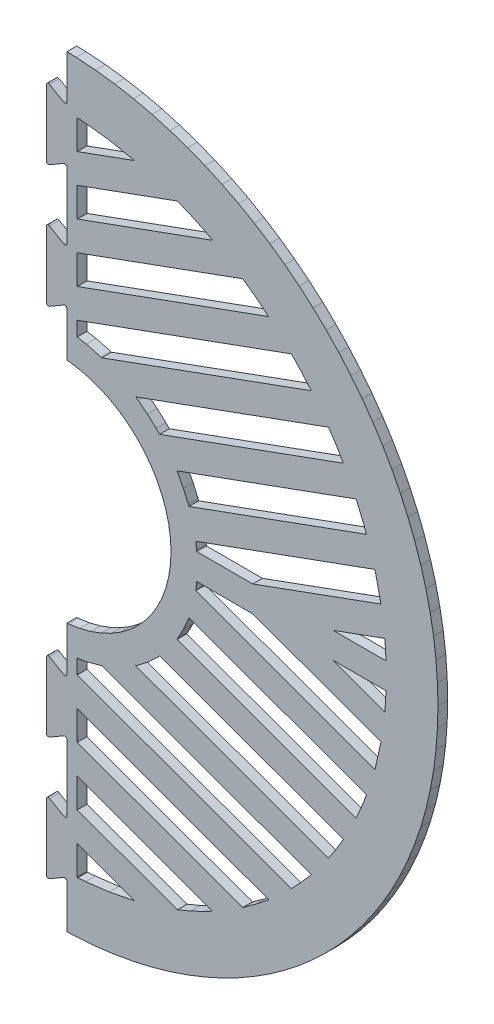
SolidWorks part; units mm, degrees
ref_plane "Front Plane" through (0, 0, 0) normal (0, 0, 1) x (1, 0, 0)
ref_plane "Top Plane" through (0, 0, 0) normal (0, 1, 0) x (1, 0, 0)
ref_plane "Right Plane" through (0, 0, 0) normal (1, 0, 0) x (0, 0, -1)
sketch "Model" plane through (0, 0, 0) normal (0, 0, 1) x (1, 0, 0)
  line L0 (-29.1025, -97.3667) -> (-27.1353, -97.9361)
  line L1 (-27.1353, -97.9361) -> (-21.8097, -99.2536)
  line L2 (-21.8097, -99.2536) -> (-16.3779, -100.2869)
  line L3 (-16.3779, -100.2869) -> (-10.848, -101.0278)
  line L4 (-10.848, -101.0278) -> (-5.2283, -101.4679)
  line L5 (-5.2283, -101.4679) -> (-4, -101.5146)
  line L6 (-4, -101.5146) -> (-4, -97.3667)
  line L7 (-4, -97.3667) -> (-29.1025, -97.3667)
  line L8 (4, -91.5563) -> (4, -100.5663)
  line L9 (4, -100.5663) -> (6.4923, -101.4734)
  line L10 (6.4923, -101.4734) -> (8.9399, -101.2903)
  line L11 (8.9399, -101.2903) -> (16.2223, -100.3929)
  line L12 (16.2223, -100.3929) -> (23.3353, -98.9929)
  line L13 (23.3353, -98.9929) -> (23.9888, -98.8316)
  line L14 (23.9888, -98.8316) -> (4, -91.5563)
  line L15 (-62.0452, -80.4333) -> (-59.3119, -82.4998)
  line L16 (-59.3119, -82.4998) -> (-55.4039, -85.1786)
  line L17 (-55.4039, -85.1786) -> (-51.3677, -87.677)
  line L18 (-51.3677, -87.677) -> (-49.1681, -88.9)
  line L19 (-49.1681, -88.9) -> (-4, -88.9)
  line L20 (-4, -88.9) -> (-4, -80.4333)
  line L21 (-4, -80.4333) -> (-62.0452, -80.4333)
  line L22 (4, -73.5362) -> (4, -82.5462)
  line L23 (4, -82.5462) -> (37.2469, -94.6471)
  line L24 (37.2469, -94.6471) -> (41.3341, -92.9428)
  line L25 (41.3341, -92.9428) -> (45.5839, -90.9334)
  line L26 (45.5839, -90.9334) -> (48.1117, -89.5915)
  line L27 (48.1117, -89.5915) -> (4, -73.5362)
  line L28 (-79.2988, -63.5) -> (-76.7248, -66.6048)
  line L29 (-76.7248, -66.6048) -> (-73.5451, -70.098)
  line L30 (-73.5451, -70.098) -> (-71.6792, -71.9667)
  line L31 (-71.6792, -71.9667) -> (-4, -71.9667)
  line L32 (-4, -71.9667) -> (-4, -63.5)
  line L33 (-4, -63.5) -> (-79.2988, -63.5)
  line L34 (4, -55.5161) -> (4, -64.5262)
  line L35 (4, -64.5262) -> (57.3994, -83.962)
  line L36 (57.3994, -83.962) -> (57.6454, -83.8007)
  line L37 (57.6454, -83.8007) -> (61.4183, -81.0733)
  line L38 (61.4183, -81.0733) -> (65.0584, -78.18)
  line L39 (65.0584, -78.18) -> (65.4148, -77.8693)
  line L40 (65.4148, -77.8693) -> (4, -55.5161)
  line L41 (-90.3108, -46.5667) -> (-90.0607, -47.0729)
  line L42 (-90.0607, -47.0729) -> (-87.7545, -51.2354)
  line L43 (-87.7545, -51.2354) -> (-85.4115, -55.0333)
  line L44 (-85.4115, -55.0333) -> (-4, -55.0333)
  line L45 (-4, -55.0333) -> (-4, -46.5667)
  line L46 (-4, -46.5667) -> (-90.3108, -46.5667)
  line L47 (13.9184, -41.106) -> (13.6646, -41.1963)
  line L48 (13.6646, -41.1963) -> (9.1415, -42.427)
  line L49 (9.1415, -42.427) -> (4.4365, -43.1676)
  line L50 (4.4365, -43.1676) -> (4, -43.2008)
  line L51 (4, -43.2008) -> (4, -46.5061)
  line L52 (4, -46.5061) -> (72.4083, -71.4047)
  line L53 (72.4083, -71.4047) -> (75.1264, -68.5601)
  line L54 (75.1264, -68.5601) -> (78.18, -65.0584)
  line L55 (78.18, -65.0584) -> (78.5271, -64.6217)
  line L56 (78.5271, -64.6217) -> (13.9184, -41.106)
  line L57 (-97.2071, -29.6333) -> (-96.5817, -31.625)
  line L58 (-96.5817, -31.625) -> (-95.8036, -33.9098)
  line L59 (-95.8036, -33.9098) -> (-94.207, -38.1)
  line L60 (-94.207, -38.1) -> (-20.7604, -38.1)
  line L61 (-20.7604, -38.1) -> (-21.4848, -37.7079)
  line L62 (-21.4848, -37.7079) -> (-23.9895, -36.1628)
  line L63 (-23.9895, -36.1628) -> (-26.3777, -34.4565)
  line L64 (-26.3777, -34.4565) -> (-28.6418, -32.5965)
  line L65 (-28.6418, -32.5965) -> (-30.7744, -30.5904)
  line L66 (-30.7744, -30.5904) -> (-31.6842, -29.6333)
  line L67 (-31.6842, -29.6333) -> (-97.2071, -29.6333)
  line L68 (31.7453, -29.5744) -> (30.6825, -30.6825)
  line L69 (30.6825, -30.6825) -> (28.0009, -33.1492)
  line L70 (28.0009, -33.1492) -> (25.1189, -35.3861)
  line L71 (25.1189, -35.3861) -> (24.3655, -35.8984)
  line L72 (24.3655, -35.8984) -> (83.8612, -57.5531)
  line L73 (83.8612, -57.5531) -> (86.3569, -53.745)
  line L74 (86.3569, -53.745) -> (88.4468, -50.2121)
  line L75 (88.4468, -50.2121) -> (31.7453, -29.5744)
  line L76 (40.7776, -14.8418) -> (40.5732, -15.4165)
  line L77 (40.5732, -15.4165) -> (39.1128, -18.8121)
  line L78 (39.1128, -18.8121) -> (37.3789, -22.0511)
  line L79 (37.3789, -22.0511) -> (37.0937, -22.511)
  line L80 (37.0937, -22.511) -> (92.3359, -42.6176)
  line L81 (92.3359, -42.6176) -> (92.9428, -41.3341)
  line L82 (92.9428, -41.3341) -> (94.7589, -36.9789)
  line L83 (94.7589, -36.9789) -> (95.5572, -34.78)
  line L84 (95.5572, -34.78) -> (40.7776, -14.8418)
  line L85 (-100.8122, -12.7) -> (-100.5006, -14.9994)
  line L86 (-100.5006, -14.9994) -> (-99.6609, -19.8552)
  line L87 (-99.6609, -19.8552) -> (-99.3846, -21.1667)
  line L88 (-99.3846, -21.1667) -> (-37.8853, -21.1667)
  line L89 (-37.8853, -21.1667) -> (-38.7638, -19.5198)
  line L90 (-38.7638, -19.5198) -> (-40.0074, -16.8291)
  line L91 (-40.0074, -16.8291) -> (-41.069, -14.0429)
  line L92 (-41.069, -14.0429) -> (-41.4935, -12.7)
  line L93 (-41.4935, -12.7) -> (-100.8122, -12.7)
  line L94 (85.2546, -4) -> (101.2046, -9.8053)
  line L95 (101.2046, -9.8053) -> (101.2903, -8.9399)
  line L96 (101.2903, -8.9399) -> (101.6001, -4)
  line L97 (101.6001, -4) -> (85.2546, -4)
  line L98 (43.2008, -4) -> (43.1676, -4.4365)
  line L99 (43.1676, -4.4365) -> (42.932, -6.3385)
  line L100 (42.932, -6.3385) -> (42.8879, -6.5999)
  line L101 (42.8879, -6.5999) -> (98.134, -26.7078)
  line L102 (98.134, -26.7078) -> (98.4177, -25.6655)
  line L103 (98.4177, -25.6655) -> (99.9812, -18.6131)
  line L104 (99.9812, -18.6131) -> (100.0206, -18.3844)
  line L105 (100.0206, -18.3844) -> (60.4997, -4)
  line L106 (60.4997, -4) -> (43.2008, -4)
  line L107 (-101.5066, 4.2333) -> (-101.5689, 2.5406)
  line L108 (-101.5689, 2.5406) -> (-101.6001, 0)
  line L109 (-101.6001, 0) -> (-101.5689, -2.5406)
  line L110 (-101.5689, -2.5406) -> (-101.5066, -4.2333)
  line L111 (-101.5066, -4.2333) -> (-43.1862, -4.2333)
  line L112 (-43.1862, -4.2333) -> (-43.1946, -4.1628)
  line L113 (-43.1946, -4.1628) -> (-43.342, -2.0942)
  line L114 (-43.342, -2.0942) -> (-43.3917, 0)
  line L115 (-43.3917, 0) -> (-43.342, 2.0942)
  line L116 (-43.342, 2.0942) -> (-43.1946, 4.1628)
  line L117 (-43.1946, 4.1628) -> (-43.1862, 4.2333)
  line L118 (-43.1862, 4.2333) -> (-101.5066, 4.2333)
  line L119 (101.2046, 9.8053) -> (85.2546, 4)
  line L120 (85.2546, 4) -> (101.6001, 4)
  line L121 (101.6001, 4) -> (101.2903, 8.9399)
  line L122 (101.2903, 8.9399) -> (101.2046, 9.8053)
  line L123 (-99.3846, 21.1667) -> (-99.6609, 19.8552)
  line L124 (-99.6609, 19.8552) -> (-100.5006, 14.9994)
  line L125 (-100.5006, 14.9994) -> (-100.8122, 12.7)
  line L126 (-100.8122, 12.7) -> (-41.4935, 12.7)
  line L127 (-41.4935, 12.7) -> (-41.069, 14.0429)
  line L128 (-41.069, 14.0429) -> (-40.0074, 16.8291)
  line L129 (-40.0074, 16.8291) -> (-38.7638, 19.5198)
  line L130 (-38.7638, 19.5198) -> (-37.8853, 21.1667)
  line L131 (-37.8853, 21.1667) -> (-99.3846, 21.1667)
  line L132 (98.134, 26.7078) -> (42.8879, 6.5999)
  line L133 (42.8879, 6.5999) -> (42.932, 6.3385)
  line L134 (42.932, 6.3385) -> (43.1676, 4.4366)
  line L135 (43.1676, 4.4366) -> (43.2008, 4)
  line L136 (43.2008, 4) -> (60.4997, 4)
  line L137 (60.4997, 4) -> (100.0206, 18.3844)
  line L138 (100.0206, 18.3844) -> (99.9812, 18.6131)
  line L139 (99.9812, 18.6131) -> (98.4177, 25.6655)
  line L140 (98.4177, 25.6655) -> (98.134, 26.7078)
  line L141 (0, 35.2778) -> (-3.607, 35.0956)
  line L142 (-3.607, 35.0956) -> (-7.1097, 34.5611)
  line L143 (-7.1097, 34.5611) -> (-10.4905, 33.6918)
  line L144 (-10.4905, 33.6918) -> (-13.7317, 32.5055)
  line L145 (-13.7317, 32.5055) -> (-16.8155, 31.0199)
  line L146 (-16.8155, 31.0199) -> (-19.7241, 29.2529)
  line L147 (-19.7241, 29.2529) -> (-22.4399, 27.2221)
  line L148 (-22.4399, 27.2221) -> (-24.9452, 24.9452)
  line L149 (-24.9452, 24.9452) -> (-27.2221, 22.4399)
  line L150 (-27.2221, 22.4399) -> (-29.2529, 19.7241)
  line L151 (-29.2529, 19.7241) -> (-31.0199, 16.8155)
  line L152 (-31.0199, 16.8155) -> (-32.5055, 13.7317)
  line L153 (-32.5055, 13.7317) -> (-33.6918, 10.4905)
  line L154 (-33.6918, 10.4905) -> (-34.5611, 7.1097)
  line L155 (-34.5611, 7.1097) -> (-35.0956, 3.607)
  line L156 (-35.0956, 3.607) -> (-35.2778, 0)
  line L157 (-35.2778, 0) -> (-35.0956, -3.607)
  line L158 (-35.0956, -3.607) -> (-34.5611, -7.1097)
  line L159 (-34.5611, -7.1097) -> (-33.6918, -10.4905)
  line L160 (-33.6918, -10.4905) -> (-32.5055, -13.7317)
  line L161 (-32.5055, -13.7317) -> (-31.0199, -16.8155)
  line L162 (-31.0199, -16.8155) -> (-29.2529, -19.7241)
  line L163 (-29.2529, -19.7241) -> (-27.2221, -22.4399)
  line L164 (-27.2221, -22.4399) -> (-24.9452, -24.9452)
  line L165 (-24.9452, -24.9452) -> (-22.4399, -27.222)
  line L166 (-22.4399, -27.222) -> (-19.7241, -29.2529)
  line L167 (-19.7241, -29.2529) -> (-16.8155, -31.0199)
  line L168 (-16.8155, -31.0199) -> (-13.7317, -32.5055)
  line L169 (-13.7317, -32.5055) -> (-10.4905, -33.6918)
  line L170 (-10.4905, -33.6918) -> (-7.1097, -34.5611)
  line L171 (-7.1097, -34.5611) -> (-3.607, -35.0956)
  line L172 (-3.607, -35.0956) -> (0, -35.2778)
  line L173 (0, -35.2778) -> (3.607, -35.0956)
  line L174 (3.607, -35.0956) -> (7.1097, -34.5611)
  line L175 (7.1097, -34.5611) -> (10.4905, -33.6918)
  line L176 (10.4905, -33.6918) -> (13.7317, -32.5055)
  line L177 (13.7317, -32.5055) -> (16.8155, -31.0199)
  line L178 (16.8155, -31.0199) -> (19.7241, -29.2529)
  line L179 (19.7241, -29.2529) -> (22.4399, -27.222)
  line L180 (22.4399, -27.222) -> (24.9452, -24.9452)
  line L181 (24.9452, -24.9452) -> (27.222, -22.4399)
  line L182 (27.222, -22.4399) -> (29.2529, -19.7241)
  line L183 (29.2529, -19.7241) -> (31.0199, -16.8155)
  line L184 (31.0199, -16.8155) -> (32.5055, -13.7317)
  line L185 (32.5055, -13.7317) -> (33.6918, -10.4905)
  line L186 (33.6918, -10.4905) -> (34.5611, -7.1097)
  line L187 (34.5611, -7.1097) -> (35.0956, -3.607)
  line L188 (35.0956, -3.607) -> (35.2778, 0)
  line L189 (35.2778, 0) -> (35.0956, 3.607)
  line L190 (35.0956, 3.607) -> (34.5611, 7.1097)
  line L191 (34.5611, 7.1097) -> (33.6918, 10.4905)
  line L192 (33.6918, 10.4905) -> (32.5055, 13.7317)
  line L193 (32.5055, 13.7317) -> (31.0199, 16.8155)
  line L194 (31.0199, 16.8155) -> (29.2529, 19.7241)
  line L195 (29.2529, 19.7241) -> (27.222, 22.4399)
  line L196 (27.222, 22.4399) -> (24.9452, 24.9452)
  line L197 (24.9452, 24.9452) -> (22.4399, 27.2221)
  line L198 (22.4399, 27.2221) -> (19.7241, 29.2529)
  line L199 (19.7241, 29.2529) -> (16.8155, 31.0199)
  line L200 (16.8155, 31.0199) -> (13.7317, 32.5055)
  line L201 (13.7317, 32.5055) -> (10.4905, 33.6918)
  line L202 (10.4905, 33.6918) -> (7.1097, 34.5611)
  line L203 (7.1097, 34.5611) -> (3.607, 35.0956)
  line L204 (3.607, 35.0956) -> (0, 35.2778)
  line L205 (-94.207, 38.1) -> (-95.8036, 33.9098)
  line L206 (-95.8036, 33.9098) -> (-96.5817, 31.625)
  line L207 (-96.5817, 31.625) -> (-97.2071, 29.6333)
  line L208 (-97.2071, 29.6333) -> (-31.6842, 29.6333)
  line L209 (-31.6842, 29.6333) -> (-30.7744, 30.5904)
  line L210 (-30.7744, 30.5904) -> (-28.6418, 32.5965)
  line L211 (-28.6418, 32.5965) -> (-26.3777, 34.4565)
  line L212 (-26.3777, 34.4565) -> (-23.9895, 36.1628)
  line L213 (-23.9895, 36.1628) -> (-21.4848, 37.7079)
  line L214 (-21.4848, 37.7079) -> (-20.7604, 38.1)
  line L215 (-20.7604, 38.1) -> (-94.207, 38.1)
  line L216 (92.3359, 42.6176) -> (37.0937, 22.511)
  line L217 (37.0937, 22.511) -> (37.3789, 22.0511)
  line L218 (37.3789, 22.0511) -> (39.1128, 18.8121)
  line L219 (39.1128, 18.8121) -> (40.5732, 15.4165)
  line L220 (40.5732, 15.4165) -> (40.7776, 14.8418)
  line L221 (40.7776, 14.8418) -> (95.5572, 34.78)
  line L222 (95.5572, 34.78) -> (94.7589, 36.9789)
  line L223 (94.7589, 36.9789) -> (92.9428, 41.3341)
  line L224 (92.9428, 41.3341) -> (92.3359, 42.6176)
  line L225 (-85.4115, 55.0333) -> (-87.7545, 51.2354)
  line L226 (-87.7545, 51.2354) -> (-90.0607, 47.0729)
  line L227 (-90.0607, 47.0729) -> (-90.3108, 46.5667)
  line L228 (-90.3108, 46.5667) -> (-4, 46.5667)
  line L229 (-4, 46.5667) -> (-4, 55.0333)
  line L230 (-4, 55.0333) -> (-85.4115, 55.0333)
  line L231 (83.8612, 57.5531) -> (24.3655, 35.8984)
  line L232 (24.3655, 35.8984) -> (25.1189, 35.3861)
  line L233 (25.1189, 35.3861) -> (28.0009, 33.1492)
  line L234 (28.0009, 33.1492) -> (30.6825, 30.6825)
  line L235 (30.6825, 30.6825) -> (31.7453, 29.5744)
  line L236 (31.7453, 29.5744) -> (88.4468, 50.2121)
  line L237 (88.4468, 50.2121) -> (86.3569, 53.745)
  line L238 (86.3569, 53.745) -> (83.8612, 57.5531)
  line L239 (72.4083, 71.4047) -> (4, 46.5061)
  line L240 (4, 46.5061) -> (4, 43.2008)
  line L241 (4, 43.2008) -> (4.4365, 43.1676)
  line L242 (4.4365, 43.1676) -> (9.1415, 42.427)
  line L243 (9.1415, 42.427) -> (13.6646, 41.1963)
  line L244 (13.6646, 41.1963) -> (13.9184, 41.106)
  line L245 (13.9184, 41.106) -> (78.5271, 64.6217)
  line L246 (78.5271, 64.6217) -> (78.18, 65.0584)
  line L247 (78.18, 65.0584) -> (75.1264, 68.5601)
  line L248 (75.1264, 68.5601) -> (72.4083, 71.4047)
  line L249 (-71.6792, 71.9667) -> (-73.5451, 70.098)
  line L250 (-73.5451, 70.098) -> (-76.7248, 66.6048)
  line L251 (-76.7248, 66.6048) -> (-79.2988, 63.5)
  line L252 (-79.2988, 63.5) -> (-4, 63.5)
  line L253 (-4, 63.5) -> (-4, 71.9667)
  line L254 (-4, 71.9667) -> (-71.6792, 71.9667)
  line L255 (57.3994, 83.9619) -> (4, 64.5262)
  line L256 (4, 64.5262) -> (4, 55.5161)
  line L257 (4, 55.5161) -> (65.4147, 77.8693)
  line L258 (65.4147, 77.8693) -> (65.0584, 78.18)
  line L259 (65.0584, 78.18) -> (61.4183, 81.0733)
  line L260 (61.4183, 81.0733) -> (57.6454, 83.8007)
  line L261 (57.6454, 83.8007) -> (57.3994, 83.9619)
  line L262 (-49.1681, 88.9) -> (-51.3677, 87.677)
  line L263 (-51.3677, 87.677) -> (-55.4039, 85.1786)
  line L264 (-55.4039, 85.1786) -> (-59.3119, 82.4998)
  line L265 (-59.3119, 82.4998) -> (-62.0452, 80.4333)
  line L266 (-62.0452, 80.4333) -> (-4, 80.4333)
  line L267 (-4, 80.4333) -> (-4, 88.9)
  line L268 (-4, 88.9) -> (-49.1681, 88.9)
  line L269 (37.2469, 94.6471) -> (4, 82.5462)
  line L270 (4, 82.5462) -> (4, 73.5362)
  line L271 (4, 73.5362) -> (48.1116, 89.5915)
  line L272 (48.1116, 89.5915) -> (45.5839, 90.9334)
  line L273 (45.5839, 90.9334) -> (41.3341, 92.9428)
  line L274 (41.3341, 92.9428) -> (37.2469, 94.6471)
  line L275 (6.4923, 101.4734) -> (4, 100.5663)
  line L276 (4, 100.5663) -> (4, 91.5563)
  line L277 (4, 91.5563) -> (23.9888, 98.8316)
  line L278 (23.9888, 98.8316) -> (23.3353, 98.9929)
  line L279 (23.3353, 98.9929) -> (16.2223, 100.3929)
  line L280 (16.2223, 100.3929) -> (8.9399, 101.2903)
  line L281 (8.9399, 101.2903) -> (6.4923, 101.4734)
  line L282 (-4, 101.5146) -> (-5.2283, 101.4679)
  line L283 (-5.2283, 101.4679) -> (-10.848, 101.0278)
  line L284 (-10.848, 101.0278) -> (-16.3779, 100.2869)
  line L285 (-16.3779, 100.2869) -> (-21.8097, 99.2536)
  line L286 (-21.8097, 99.2536) -> (-27.1353, 97.9361)
  line L287 (-27.1353, 97.9361) -> (-29.1025, 97.3667)
  line L288 (-29.1025, 97.3667) -> (-4, 97.3667)
  line L289 (-4, 97.3667) -> (-4, 101.5146)
  line L290 (0, 117.6001) -> (6.0517, 117.4471)
  line L291 (6.0517, 117.4471) -> (12.0239, 116.9929)
  line L292 (12.0239, 116.9929) -> (17.9093, 116.2451)
  line L293 (17.9093, 116.2451) -> (23.7005, 115.2109)
  line L294 (23.7005, 115.2109) -> (29.3901, 113.8977)
  line L295 (29.3901, 113.8977) -> (34.9707, 112.313)
  line L296 (34.9707, 112.313) -> (40.4348, 110.4642)
  line L297 (40.4348, 110.4642) -> (45.7753, 108.3585)
  line L298 (45.7753, 108.3585) -> (50.9845, 106.0035)
  line L299 (50.9845, 106.0035) -> (56.0552, 103.4064)
  line L300 (56.0552, 103.4064) -> (60.9799, 100.5747)
  line L301 (60.9799, 100.5747) -> (65.7513, 97.5159)
  line L302 (65.7513, 97.5159) -> (70.362, 94.2371)
  line L303 (70.362, 94.2371) -> (74.8046, 90.746)
  line L304 (74.8046, 90.746) -> (79.0716, 87.0497)
  line L305 (79.0716, 87.0497) -> (83.1558, 83.1558)
  line L306 (83.1558, 83.1558) -> (87.0497, 79.0717)
  line L307 (87.0497, 79.0717) -> (90.7459, 74.8046)
  line L308 (90.7459, 74.8046) -> (94.2371, 70.362)
  line L309 (94.2371, 70.362) -> (97.5158, 65.7513)
  line L310 (97.5158, 65.7513) -> (100.5747, 60.9799)
  line L311 (100.5747, 60.9799) -> (103.4064, 56.0552)
  line L312 (103.4064, 56.0552) -> (106.0035, 50.9845)
  line L313 (106.0035, 50.9845) -> (108.3585, 45.7753)
  line L314 (108.3585, 45.7753) -> (110.4642, 40.4349)
  line L315 (110.4642, 40.4349) -> (112.313, 34.9707)
  line L316 (112.313, 34.9707) -> (113.8977, 29.3901)
  line L317 (113.8977, 29.3901) -> (115.2109, 23.7005)
  line L318 (115.2109, 23.7005) -> (116.2451, 17.9093)
  line L319 (116.2451, 17.9093) -> (116.9929, 12.0239)
  line L320 (116.9929, 12.0239) -> (117.4471, 6.0517)
  line L321 (117.4471, 6.0517) -> (117.6001, 0)
  line L322 (117.6001, 0) -> (117.4471, -6.0517)
  line L323 (117.4471, -6.0517) -> (116.9929, -12.0239)
  line L324 (116.9929, -12.0239) -> (116.2451, -17.9093)
  line L325 (116.2451, -17.9093) -> (115.2109, -23.7005)
  line L326 (115.2109, -23.7005) -> (113.8977, -29.3901)
  line L327 (113.8977, -29.3901) -> (112.313, -34.9707)
  line L328 (112.313, -34.9707) -> (110.4642, -40.4348)
  line L329 (110.4642, -40.4348) -> (108.3585, -45.7753)
  line L330 (108.3585, -45.7753) -> (106.0035, -50.9845)
  line L331 (106.0035, -50.9845) -> (103.4064, -56.0552)
  line L332 (103.4064, -56.0552) -> (100.5747, -60.9799)
  line L333 (100.5747, -60.9799) -> (97.5158, -65.7513)
  line L334 (97.5158, -65.7513) -> (94.2371, -70.362)
  line L335 (94.2371, -70.362) -> (90.7459, -74.8046)
  line L336 (90.7459, -74.8046) -> (87.0497, -79.0716)
  line L337 (87.0497, -79.0716) -> (83.1558, -83.1558)
  line L338 (83.1558, -83.1558) -> (79.0716, -87.0497)
  line L339 (79.0716, -87.0497) -> (74.8046, -90.7459)
  line L340 (74.8046, -90.7459) -> (70.362, -94.2371)
  line L341 (70.362, -94.2371) -> (65.7513, -97.5158)
  line L342 (65.7513, -97.5158) -> (60.9799, -100.5747)
  line L343 (60.9799, -100.5747) -> (56.0552, -103.4064)
  line L344 (56.0552, -103.4064) -> (50.9845, -106.0035)
  line L345 (50.9845, -106.0035) -> (45.7753, -108.3585)
  line L346 (45.7753, -108.3585) -> (40.4348, -110.4642)
  line L347 (40.4348, -110.4642) -> (34.9707, -112.313)
  line L348 (34.9707, -112.313) -> (29.3901, -113.8977)
  line L349 (29.3901, -113.8977) -> (23.7005, -115.2109)
  line L350 (23.7005, -115.2109) -> (17.9093, -116.2451)
  line L351 (17.9093, -116.2451) -> (12.0239, -116.9929)
  line L352 (12.0239, -116.9929) -> (6.0517, -117.4471)
  line L353 (6.0517, -117.4471) -> (0, -117.6001)
  line L354 (0, -117.6001) -> (-6.0517, -117.4471)
  line L355 (-6.0517, -117.4471) -> (-12.0239, -116.9929)
  line L356 (-12.0239, -116.9929) -> (-17.9093, -116.2451)
  line L357 (-17.9093, -116.2451) -> (-23.7005, -115.2109)
  line L358 (-23.7005, -115.2109) -> (-29.3901, -113.8977)
  line L359 (-29.3901, -113.8977) -> (-34.9707, -112.313)
  line L360 (-34.9707, -112.313) -> (-40.4349, -110.4642)
  line L361 (-40.4349, -110.4642) -> (-45.7753, -108.3585)
  line L362 (-45.7753, -108.3585) -> (-50.9845, -106.0035)
  line L363 (-50.9845, -106.0035) -> (-56.0552, -103.4064)
  line L364 (-56.0552, -103.4064) -> (-60.9799, -100.5747)
  line L365 (-60.9799, -100.5747) -> (-65.7513, -97.5158)
  line L366 (-65.7513, -97.5158) -> (-70.362, -94.2371)
  line L367 (-70.362, -94.2371) -> (-74.8046, -90.7459)
  line L368 (-74.8046, -90.7459) -> (-79.0717, -87.0497)
  line L369 (-79.0717, -87.0497) -> (-83.1558, -83.1558)
  line L370 (-83.1558, -83.1558) -> (-87.0497, -79.0716)
  line L371 (-87.0497, -79.0716) -> (-90.746, -74.8046)
  line L372 (-90.746, -74.8046) -> (-94.2371, -70.362)
  line L373 (-94.2371, -70.362) -> (-97.5159, -65.7513)
  line L374 (-97.5159, -65.7513) -> (-100.5747, -60.9799)
  line L375 (-100.5747, -60.9799) -> (-103.4064, -56.0552)
  line L376 (-103.4064, -56.0552) -> (-106.0035, -50.9845)
  line L377 (-106.0035, -50.9845) -> (-108.3585, -45.7753)
  line L378 (-108.3585, -45.7753) -> (-110.4642, -40.4348)
  line L379 (-110.4642, -40.4348) -> (-112.313, -34.9707)
  line L380 (-112.313, -34.9707) -> (-113.8977, -29.3901)
  line L381 (-113.8977, -29.3901) -> (-115.2109, -23.7005)
  line L382 (-115.2109, -23.7005) -> (-116.2451, -17.9093)
  line L383 (-116.2451, -17.9093) -> (-116.9929, -12.0239)
  line L384 (-116.9929, -12.0239) -> (-117.4471, -6.0517)
  line L385 (-117.4471, -6.0517) -> (-117.6001, 0)
  line L386 (-117.6001, 0) -> (-117.4471, 6.0517)
  line L387 (-117.4471, 6.0517) -> (-116.9929, 12.0239)
  line L388 (-116.9929, 12.0239) -> (-116.2451, 17.9093)
  line L389 (-116.2451, 17.9093) -> (-115.2109, 23.7005)
  line L390 (-115.2109, 23.7005) -> (-113.8977, 29.3901)
  line L391 (-113.8977, 29.3901) -> (-112.313, 34.9707)
  line L392 (-112.313, 34.9707) -> (-110.4642, 40.4349)
  line L393 (-110.4642, 40.4349) -> (-108.3585, 45.7753)
  line L394 (-108.3585, 45.7753) -> (-106.0035, 50.9845)
  line L395 (-106.0035, 50.9845) -> (-103.4064, 56.0552)
  line L396 (-103.4064, 56.0552) -> (-100.5747, 60.9799)
  line L397 (-100.5747, 60.9799) -> (-97.5159, 65.7513)
  line L398 (-97.5159, 65.7513) -> (-94.2371, 70.362)
  line L399 (-94.2371, 70.362) -> (-90.746, 74.8046)
  line L400 (-90.746, 74.8046) -> (-87.0497, 79.0717)
  line L401 (-87.0497, 79.0717) -> (-83.1558, 83.1558)
  line L402 (-83.1558, 83.1558) -> (-79.0717, 87.0497)
  line L403 (-79.0717, 87.0497) -> (-74.8046, 90.746)
  line L404 (-74.8046, 90.746) -> (-70.362, 94.2371)
  line L405 (-70.362, 94.2371) -> (-65.7513, 97.5159)
  line L406 (-65.7513, 97.5159) -> (-60.9799, 100.5747)
  line L407 (-60.9799, 100.5747) -> (-56.0552, 103.4064)
  line L408 (-56.0552, 103.4064) -> (-50.9845, 106.0035)
  line L409 (-50.9845, 106.0035) -> (-45.7753, 108.3585)
  line L410 (-45.7753, 108.3585) -> (-40.4349, 110.4642)
  line L411 (-40.4349, 110.4642) -> (-34.9707, 112.313)
  line L412 (-34.9707, 112.313) -> (-29.3901, 113.8977)
  line L413 (-29.3901, 113.8977) -> (-23.7005, 115.2109)
  line L414 (-23.7005, 115.2109) -> (-17.9093, 116.2451)
  line L415 (-17.9093, 116.2451) -> (-12.0239, 116.9929)
  line L416 (-12.0239, 116.9929) -> (-6.0517, 117.4471)
  line L417 (-6.0517, 117.4471) -> (0, 117.6001)
extrude "Boss-Extrude1" add sketch "Model" along normal blind 3
sketch "Sketch1" plane through (0, 0, 3) normal (0, 0, 1) x (1, 0, 0)
  line L0 (-71.6562, 0) -> (-89.062, 0) construction
  line L1 (0, 55.4106) -> (0, 79.2155) construction
  line L2 (0, 200.1765) -> (0, 9.3221) construction
  line L6 (88.0963, 0) -> (149.8301, 0) construction
  line L7 (-6.35, -35.2778) -> (6.35, -35.2778)
  line L8 (-6.35, 113.995) -> (6.35, 113.995)
  line L9 (-6.35, 113.995) -> (-6.35, 35.2778)
  line L10 (-6.35, 35.2778) -> (6.35, 35.2778)
  line L11 (6.35, 113.995) -> (6.35, 35.2778)
  line L12 (-6.35, 113.995) -> (6.35, 35.2778) construction
  line L13 (-6.35, 35.2778) -> (6.35, 113.995) construction
  line L14 (6.35, -113.995) -> (6.35, -35.2778)
  line L15 (-6.35, -113.995) -> (-6.35, -35.2778)
  line L16 (-6.35, -113.995) -> (6.35, -113.995)
  line L17 (-76.6035, 4.2333) -> (-66.7089, -4.2333) construction
  line L18 (-43.1862, 4.2333) -> (-101.5066, 4.2333) construction
  line L19 (-101.5066, -4.2333) -> (-43.1862, -4.2333) construction
  line L20 (-4, 50.8) -> (4, 60.0211) construction
  line L21 (-4, 46.5667) -> (-4, 55.0333) construction
  line L22 (4, 64.5262) -> (4, 55.5161) construction
  point P15 (0, 0)
  point P16 (0, 74.6364)
  dimension "D1" = 12.7
extrude "Boss-Extrude2" add sketch "Sketch1" against normal up to surface (3 mm away) up to face at (12.4255, 99.0148, 0)
ref_plane "Plane1" through (0, 0, 0) normal (1, 0, 0) x (0, 0, -1)
ref_plane "Plane2" through (0, 0, 0) normal (0, -1, 0) x (-1, 0, 0)
ref_axis "Axis1" through (0, 0, 3.15) along (0, 0, -1)
sketch "Sketch4" plane through (0, 0, 3) normal (0, 0, 1) x (1, 0, 0)
  line L0 (0, 262.4993) -> (0, -109.6215) construction
  line L1 (0, -1.65) -> (0, 1.65) construction
  line L2 (-3.175, 106.6313) -> (-3.175, 84.0589)
  line L3 (3.175, 252.3742) -> (3.175, 102.9651)
  line L4 (-3.175, 106.6313) -> (3.175, 102.9651)
  line L5 (132.8797, 95.3451) -> (156.548, 95.3451) construction
  line L6 (-3.175, 84.0589) -> (3.175, 87.7251)
  line L7 (-3.175, 68.8189) -> (3.175, 65.1528)
  line L8 (-3.175, 46.2466) -> (3.175, 49.9128)
  line L9 (0, 116.1563) -> (163.0074, 116.1563) construction
  line L11 (3.175, 87.7251) -> (3.175, 65.1528)
  line L12 (-3.175, 68.8189) -> (-3.175, 46.2466)
  line L13 (3.175, 49.9128) -> (3.175, -49.9128)
  line L14 (-1.65, 0) -> (1.65, 0) construction
  line L15 (120.2007, 0) -> (342.421, 0) construction
  line L16 (-3.175, -68.8189) -> (-3.175, -46.2466)
  line L17 (3.175, -87.7251) -> (3.175, -65.1528)
  line L18 (-3.175, -46.2466) -> (3.175, -49.9128)
  line L19 (-3.175, -68.8189) -> (3.175, -65.1528)
  line L20 (-3.175, -84.0589) -> (3.175, -87.7251)
  line L21 (-3.175, -106.6313) -> (3.175, -102.9651)
  line L22 (3.175, -252.3742) -> (3.175, -102.9651)
  line L23 (-3.175, -106.6313) -> (-3.175, -84.0589)
  line L24 (3.175, 252.3742) -> (-257.0941, 252.3742)
  line L25 (-257.0941, 252.3742) -> (-257.0941, -252.3742)
  line L26 (-257.0941, -252.3742) -> (3.175, -252.3742)
  line L27 (0, 35.2778) -> (0, 117.6001) construction
  line L28 (0, 35.2778) -> (-3.607, 35.0956) construction
  line L29 (6.0517, 117.4471) -> (0, 117.6001) construction
  line L30 (3.175, 76.4389) -> (0, 76.4389) construction
  point P5 (3.175, 0)
  point P41 (0, 76.4389)
  dimension "D1" = 3.175
  dimension "D2" = 60
  dimension "D3" = 7.62
  dimension "D4" = 2
  dimension "D5" = 9.525
  dimension "D6" = 6.35
  dimension "D7" = 22.5723
extrude "Cut-Extrude1" cut sketch "Sketch4" against normal through all both and the other way through all
fillet "Fillet1" radius 0.635 16 edges at (3.175, 102.9651, 1.5) (-3.175, -46.2466, 1.5) (-3.175, -84.0589, 1.5) (-3.175, -106.6313, 1.5) (3.175, -102.9651, 1.5) (3.175, -87.7251, 1.5) (3.175, -49.9128, 1.5) (-3.175, -68.8189, 1.5) (3.175, -65.1528, 1.5) (-3.175, 46.2466, 1.5) (3.175, 49.9128, 1.5) (-3.175, 106.6313, 1.5) (-3.175, 84.0589, 1.5) (3.175, 65.1528, 1.5) (3.175, 87.7251, 1.5) (-3.175, 68.8189, 1.5)
